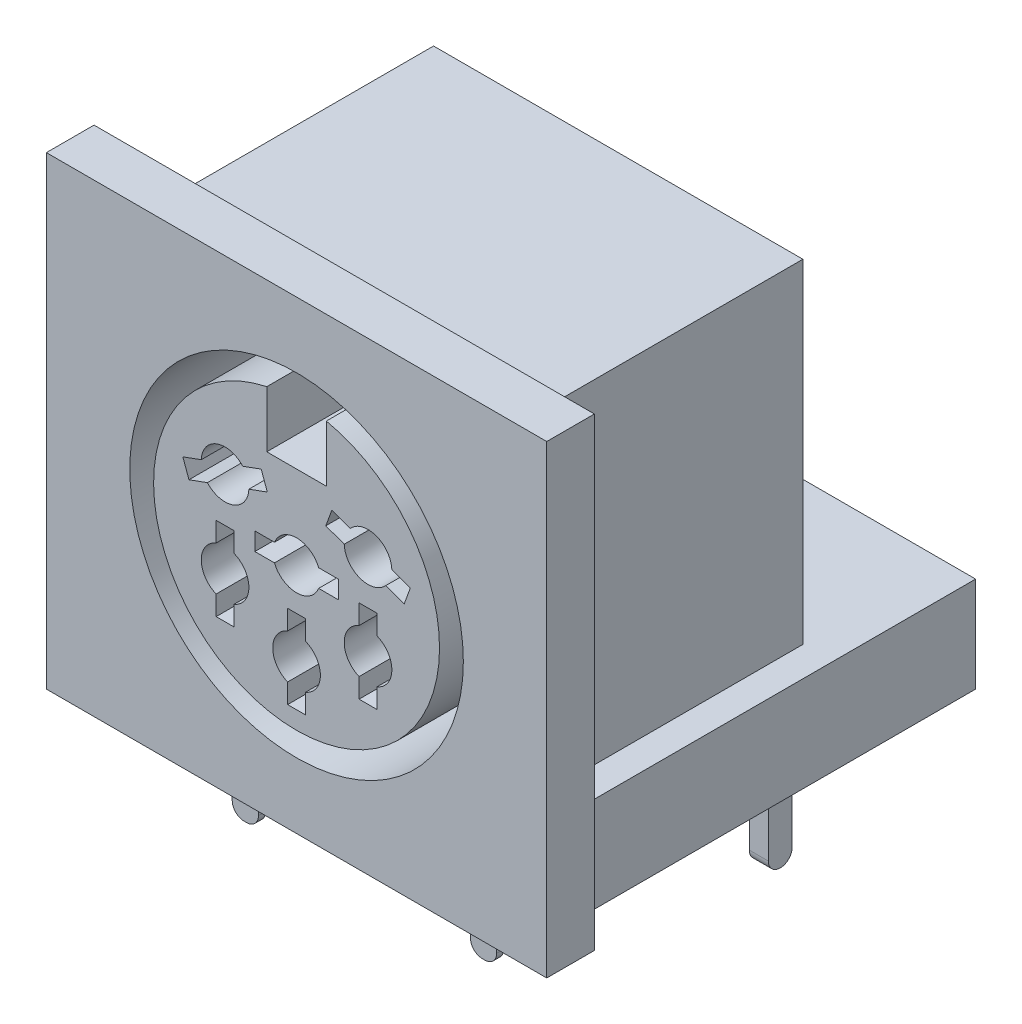
SolidWorks part; units mm, degrees
ref_plane "Спереди" through (0, 0, 0) normal (0, 0, 1) x (1, 0, 0)
ref_plane "Сверху" through (0, 0, 0) normal (0, 1, 0) x (1, 0, 0)
ref_plane "Справа" through (0, 0, 0) normal (1, 0, 0) x (0, 0, -1)
sketch "Эскиз1" plane through (0, 0, 0) normal (0, 0, 1) x (1, 0, 0)
  line L0 (-10.5, 9.75) -> (10.5, 9.75) construction
  line L1 (-10.5, 19.5) -> (10.5, 19.5)
  line L2 (-10.5, 19.5) -> (-10.5, 0)
  line L3 (-10.5, 0) -> (10.5, 0)
  line L4 (10.5, 19.5) -> (10.5, 0)
  point P4 (0, 0)
  point P8 (0, 9.75)
  dimension "D1" = 21
  dimension "D2" = 19.5
extrude "Бобышка-Вытянуть1" add sketch "Эскиз1" against normal blind 2
sketch "Эскиз2" plane through (0, 0, 0) normal (0, 0, 1) x (1, 0, 0)
  line L0 (-10.5, 9.75) -> (10.5, 9.75) construction
  line L1 (-1.25, 15.6183) -> (-1.25, 13.25)
  line L2 (-1.25, 13.25) -> (1.25, 13.25)
  line L3 (1.25, 13.25) -> (1.25, 15.6183)
  circle A0 centre (0, 9.75) radius 7
  arc A1 (-1.25, 15.6183) -> (1.25, 15.6183) centre (0, 9.75) ccw
  point P7 (0, 13.25)
  point P10 (0, 16.75)
  dimension "D1" = 14
  dimension "D2" = 1
  dimension "D3" = 2.5
  dimension "D4" = 3.5
sketch "Эскиз3" plane through (0, 0, 0) normal (0, 0, 1) x (1, 0, 0)
  line L0 (-10.5, 0) -> (10.5, 0) construction
  line L1 (-7.75, 0) -> (7.75, 0)
  line L2 (-7.75, 0) -> (-7.75, 18)
  line L3 (-7.75, 18) -> (7.75, 18)
  line L4 (7.75, 0) -> (7.75, 18)
  dimension "D1" = 15.5
  dimension "D2" = 18
extrude "Бобышка-Вытянуть2" add sketch "Эскиз3" against normal blind 13.5
sketch "Эскиз4" plane through (0, 0, 0) normal (0, 0, 1) x (1, 0, 0)
  line L0 (-10.5, 0) -> (10.5, 0) construction
  line L1 (-9, 0) -> (9, 0)
  line L2 (-9, 0) -> (-9, 4)
  line L3 (-9, 4) -> (9, 4)
  line L4 (9, 0) -> (9, 4)
  dimension "D1" = 4
  dimension "D2" = 18
extrude "Бобышка-Вытянуть3" add sketch "Эскиз4" against normal blind 19.5
extrude "Вырез-Вытянуть1" cut sketch "Эскиз2" against normal blind 10
sketch "Эскиз5" plane through (0, 0, 0) normal (0, 0, 1) x (1, 0, 0)
  line L0 (-10.5, 9.75) -> (10.5, 9.75) construction
  line L1 (-3, 7.9472) -> (3, 7.9472) construction
  line L2 (-3, 11.5528) -> (3, 11.5528) construction
  circle A0 centre (0, 9.75) radius 3.5 construction
  circle A1 centre (0, 6.25) radius 1
  circle A2 centre (-3, 7.9472) radius 1
  circle A3 centre (3, 7.9472) radius 1
  circle A4 centre (-3, 11.5528) radius 1
  circle A5 centre (3, 11.5528) radius 1
  circle A6 centre (0, 9.75) radius 1
  dimension "D1" = 7
  dimension "D2" = 2
  dimension "D3" = 6
  dimension "D4" = 6
extrude "Вырез-Вытянуть2" cut sketch "Эскиз5" against normal blind 10
sketch "Эскиз6" plane through (0, 0, 0) normal (0, 0, 1) x (1, 0, 0)
  line L0 (4.5162, 10.6019) -> (1.2273, 11.7989)
  line L1 (-3.375, 9.6972) -> (-2.625, 9.6972)
  line L2 (-3.375, 9.6972) -> (-3.375, 6.1972)
  line L3 (-3.375, 6.1972) -> (-2.625, 6.1972)
  line L4 (-2.625, 9.6972) -> (-2.625, 6.1972)
  line L5 (-3.375, 9.6972) -> (-2.625, 6.1972) construction
  line L6 (-3.375, 6.1972) -> (-2.625, 9.6972) construction
  line L7 (2.625, 9.6972) -> (3.375, 9.6972)
  line L8 (2.625, 9.6972) -> (2.625, 6.1972)
  line L9 (2.625, 6.1972) -> (3.375, 6.1972)
  line L10 (3.375, 9.6972) -> (3.375, 6.1972)
  line L11 (2.625, 9.6972) -> (3.375, 6.1972) construction
  line L12 (2.625, 6.1972) -> (3.375, 9.6972) construction
  line L13 (-0.375, 8) -> (0.375, 8)
  line L14 (-0.375, 8) -> (-0.375, 4.5)
  line L15 (-0.375, 4.5) -> (0.375, 4.5)
  line L16 (0.375, 8) -> (0.375, 4.5)
  line L17 (-0.375, 8) -> (0.375, 4.5) construction
  line L18 (-0.375, 4.5) -> (0.375, 8) construction
  line L19 (4.5162, 10.6019) -> (4.7727, 11.3066)
  line L20 (1.2273, 11.7989) -> (1.4838, 12.5037)
  line L21 (4.7727, 11.3066) -> (1.4838, 12.5037)
  line L22 (4.5162, 10.6019) -> (1.4838, 12.5037) construction
  line L23 (1.2273, 11.7989) -> (4.7727, 11.3066) construction
  line L24 (-4.5162, 10.6019) -> (-1.2273, 11.7989)
  line L25 (-4.5162, 10.6019) -> (-4.7727, 11.3066)
  line L26 (-1.2273, 11.7989) -> (-1.4838, 12.5037)
  line L27 (-4.7727, 11.3066) -> (-1.4838, 12.5037)
  line L28 (-4.5162, 10.6019) -> (-1.4838, 12.5037) construction
  line L29 (-1.2273, 11.7989) -> (-4.7727, 11.3066) construction
  line L31 (-3, 11.5528) -> (3, 11.5528) construction
  line L33 (-1.75, 9.375) -> (1.75, 9.375)
  line L34 (-1.75, 9.375) -> (-1.75, 10.125)
  line L35 (-1.75, 10.125) -> (1.75, 10.125)
  line L36 (1.75, 9.375) -> (1.75, 10.125)
  line L37 (-1.75, 9.375) -> (1.75, 10.125) construction
  line L38 (-1.75, 10.125) -> (1.75, 9.375) construction
  point P0 (-3, 7.9472)
  point P6 (3, 7.9472)
  point P12 (0, 6.25)
  point P19 (3, 11.5528)
  point P20 (-3, 11.5528)
  point P27 (0, 9.75)
  dimension "D1" = 3.5
  dimension "D2" = 0.75
  dimension "D3" = 20
  dimension "D4" = 20
extrude "Вырез-Вытянуть3" cut sketch "Эскиз6" against normal blind 10
sketch "Эскиз7" plane through (0, 0, 0) normal (0, 1, 0) x (1, 0, 0)
  line L0 (-5, 3) -> (5, 3) construction
  line L1 (-5.55, 2.85) -> (-4.45, 2.85)
  line L2 (-5.55, 2.85) -> (-5.55, 3.15)
  line L3 (-5.55, 3.15) -> (-4.45, 3.15)
  line L4 (-4.45, 2.85) -> (-4.45, 3.15)
  line L5 (-5.55, 2.85) -> (-4.45, 3.15) construction
  line L6 (-5.55, 3.15) -> (-4.45, 2.85) construction
  line L7 (4.45, 2.85) -> (5.55, 2.85)
  line L8 (4.45, 2.85) -> (4.45, 3.15)
  line L9 (4.45, 3.15) -> (5.55, 3.15)
  line L10 (5.55, 2.85) -> (5.55, 3.15)
  line L11 (4.45, 2.85) -> (5.55, 3.15) construction
  line L12 (4.45, 3.15) -> (5.55, 2.85) construction
  line L13 (-7.5, 12.4) -> (7.5, 12.4) construction
  line L14 (-5, 15) -> (5, 15) construction
  line L15 (-7.5, 17.3) -> (7.5, 17.3) construction
  line L17 (-7.9, 11.9) -> (-7.1, 11.9)
  line L18 (-7.9, 11.9) -> (-7.9, 12.9)
  line L19 (-7.9, 12.9) -> (-7.1, 12.9)
  line L20 (-7.1, 11.9) -> (-7.1, 12.9)
  line L21 (-7.9, 11.9) -> (-7.1, 12.9) construction
  line L22 (-7.9, 12.9) -> (-7.1, 11.9) construction
  line L23 (-0.4, 11.9) -> (0.4, 11.9)
  line L24 (-0.4, 11.9) -> (-0.4, 12.9)
  line L25 (-0.4, 12.9) -> (0.4, 12.9)
  line L26 (0.4, 11.9) -> (0.4, 12.9)
  line L27 (-0.4, 11.9) -> (0.4, 12.9) construction
  line L28 (-0.4, 12.9) -> (0.4, 11.9) construction
  line L29 (7.1, 11.9) -> (7.9, 11.9)
  line L30 (7.1, 11.9) -> (7.1, 12.9)
  line L31 (7.1, 12.9) -> (7.9, 12.9)
  line L32 (7.9, 11.9) -> (7.9, 12.9)
  line L33 (7.1, 11.9) -> (7.9, 12.9) construction
  line L34 (7.1, 12.9) -> (7.9, 11.9) construction
  line L35 (-5.4, 14.5) -> (-4.6, 14.5)
  line L36 (-5.4, 14.5) -> (-5.4, 15.5)
  line L37 (-5.4, 15.5) -> (-4.6, 15.5)
  line L38 (-4.6, 14.5) -> (-4.6, 15.5)
  line L39 (-5.4, 14.5) -> (-4.6, 15.5) construction
  line L40 (-5.4, 15.5) -> (-4.6, 14.5) construction
  line L41 (4.6, 14.5) -> (5.4, 14.5)
  line L42 (4.6, 14.5) -> (4.6, 15.5)
  line L43 (4.6, 15.5) -> (5.4, 15.5)
  line L44 (5.4, 14.5) -> (5.4, 15.5)
  line L45 (4.6, 14.5) -> (5.4, 15.5) construction
  line L46 (4.6, 15.5) -> (5.4, 14.5) construction
  line L47 (-0.5, 17.7) -> (0.5, 17.7)
  line L48 (-0.5, 17.7) -> (-0.5, 16.9)
  line L49 (-0.5, 16.9) -> (0.5, 16.9)
  line L50 (0.5, 17.7) -> (0.5, 16.9)
  line L51 (-0.5, 17.7) -> (0.5, 16.9) construction
  line L52 (-0.5, 16.9) -> (0.5, 17.7) construction
  point P0 (-5, 3)
  point P5 (5, 3)
  point P12 (0, 3)
  point P21 (0, 12.4)
  point P22 (0, 15)
  point P23 (0, 17.3)
  point P28 (0, 12.4)
  point P45 (0, 17.3)
  dimension "D1" = 10
  dimension "D2" = 1.1
  dimension "D3" = 0.3
  dimension "D4" = 3
  dimension "D5" = 10
  dimension "D6" = 15
  dimension "D7" = 12.4
  dimension "D8" = 15
  dimension "D9" = 17.3
  dimension "D10" = 1
  dimension "D11" = 0.8
extrude "Бобышка-Вытянуть4" add sketch "Эскиз7" against normal blind 3.5
fillet "Скругление1" radius 0.5 16 edges at (5.55, -3.5, -3) (4.45, -3.5, -3) (-4.45, -3.5, -3) (-5.55, -3.5, -3) (0.5, -3.5, -17.3) (-0.5, -3.5, -17.3) (7.5, -3.5, -12.9) (7.5, -3.5, -11.9) (5, -3.5, -15.5) (5, -3.5, -14.5) (0, -3.5, -12.9) (0, -3.5, -11.9) (-5, -3.5, -14.5) (-5, -3.5, -15.5) (-7.5, -3.5, -11.9) (-7.5, -3.5, -12.9)
